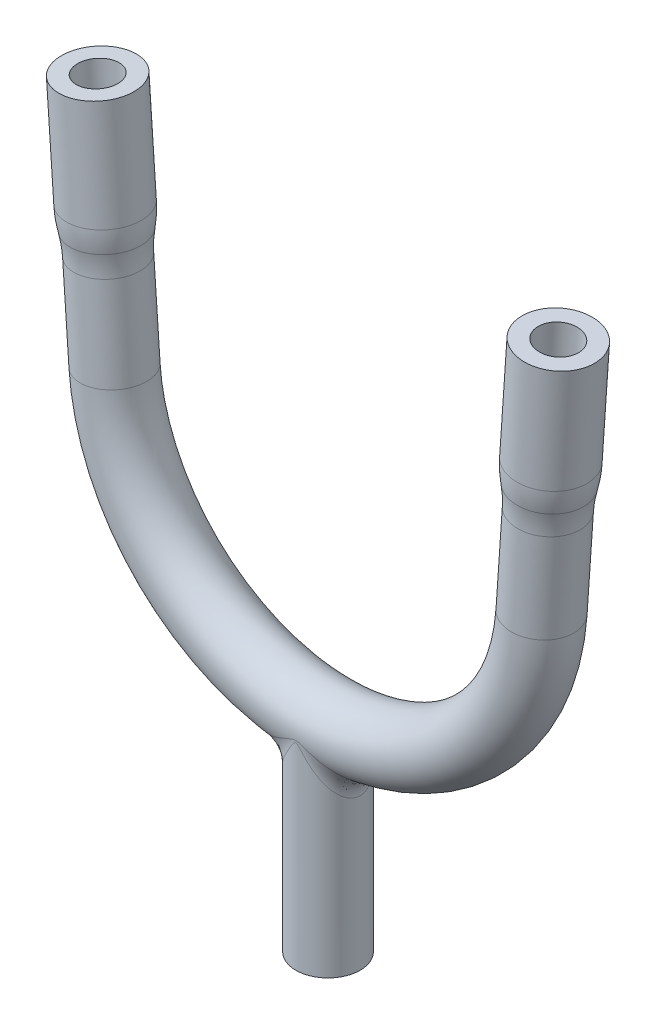
SolidWorks part; units mm, degrees
ref_plane "Alzado" through (0, 0, 0) normal (0, 0, 1) x (1, 0, 0)
ref_plane "Planta" through (0, 0, 0) normal (0, 1, 0) x (1, 0, 0)
ref_plane "Vista lateral" through (0, 0, 0) normal (1, 0, 0) x (0, 0, -1)
sketch "Croquis1" plane through (0, 0, 0) normal (0, 0, 1) x (1, 0, 0)
  line L0 (0, 0) -> (0, 191.7552) construction
  line L1 (5, 160.1093) -> (40.914, 157.6226) construction
  line L2 (40.914, 157.6226) -> (30, 0) construction
  line L3 (27.506, 0.1727) -> (38.5804, 160.1115) construction
  line L4 (27.506, 0.1727) -> (30, 0) construction
  line L5 (5, 160.1093) -> (4.8273, 157.6153) construction
  line L6 (4.8273, 157.6153) -> (-19.3231, 159.2875) construction
  line L7 (24.0182, -50.199) -> (31.2919, 54.8506) construction
  circle A0 centre (27.506, 0.1727) radius 2.5 construction
  spline S0 degree 3 poles (4.8273, 157.6153) (36.4183, 155.4279) (39.0186, 166.4413) (27.506, 0.1727) knots 0 0 0 0 1 1 1 1
  dimension "D5" = 5
  dimension "D6" = 95
  dimension "D7" = 500
  dimension "D1" = 30
  dimension "D2" = 10
  dimension "D3" = 36
  dimension "D4" = 158
ref_plane "Plano1" through (27.506, 0.1727, 0) normal (-0.0691, -0.9976, 0) x (-0.9976, 0.0691, 0)
sketch "Croquis6" plane through (0, 0, 0) normal (0, 1, 0) x (1, 0, 0)
  line L1 (-37.5, 2.5) -> (37.5, 2.5)
  line L2 (-37.5, 2.5) -> (-37.5, -2.5)
  line L3 (-37.5, -2.5) -> (37.5, -2.5)
  line L4 (37.5, 2.5) -> (37.5, -2.5)
  line L5 (-37.5, 2.5) -> (37.5, -2.5) construction
  line L6 (-37.5, -2.5) -> (37.5, 2.5) construction
  point P0 (0, 0)
  dimension "D1" = 5
  dimension "D2" = 75
sketch "Croquis11" plane through (0, 0, 0) normal (0, 0, 1) x (1, 0, 0)
  line L0 (27.506, 0.1727) -> (28.536, 15.1373)
  line L1 (0, 0) -> (0, -39.8273) construction
  line L2 (27.506, 0.1727) -> (26.4525, -15.133)
  arc A0 (0, -39.8273) -> (26.4525, -15.133) centre (0, -13.3123) ccw
  spline S0 degree 3 poles (4.8273, 157.6153) (36.4183, 155.4279) (39.0186, 166.4413) (27.506, 0.1727) knots 0 0 0 0 1 1 1 1 construction
  dimension "D1" = 15
  dimension "D2" = 40
ref_plane "Plano2" through (28.536, 15.1373, 0) normal (0.0687, 0.9976, 0) x (0.9976, -0.0687, 0)
sketch "Croquis12" plane through (28.536, 15.1373, 0) normal (0.0687, 0.9976, 0) x (0.9976, -0.0687, 0)
  circle A0 centre (0, 0) radius 4
  dimension "D1" = 8
sweep "Barrer1" add profiles "Croquis12" path "Croquis11"
sketch "Croquis13" plane through (1.1716, 17.0208, 0) normal (0.0687, 0.9976, 0) x (0.9976, -0.0687, 0)
  circle A2 centre (27.4292, 0) radius 4.5
  circle A3 centre (27.4292, 0) radius 4.5
  dimension "D1" = 0.5
extrude "Saliente-Extruir1" add sketch "Croquis13" against normal blind 15
fillet "Redondeo3" radius 15 1 edges at (23.5154, 0.4474, 0)
fillet "Redondeo4" radius 15 1 edges at (23.0166, 0.4817, 0)
mirror "Simetría7" about plane through (0, 0, 0) normal (1, 0, 0) of bodies 138
sketch "Croquis14" plane through (0, 0, 0) normal (0, 0, 1) x (1, 0, 0)
  line L0 (0, -39.8273) -> (0, -64.8273)
  line L1 (0, -35.8273) -> (0, -43.8273) construction
  dimension "D1" = 25
ref_plane "Plano3" through (0, -64.8273, 0) normal (0, -1, 0) x (-1, 0, 0)
sketch "Croquis15" plane through (0, -64.8273, 0) normal (0, -1, 0) x (-1, 0, 0)
  circle A0 centre (0, 0) radius 3.975
  dimension "D1" = 7.95
extrude "Saliente-Extruir2" add sketch "Croquis15" against normal up to vertex (25 mm away) up to point (0, -39.8273, 0)
fillet "Redondeo5" radius 3 1 edges at (-0.0002, -40.2738, -3.975)
sketch "Sketch1" plane through (1.1716, 17.0208, 0) normal (0.0687, 0.9976, 0) x (0.9976, -0.0687, 0)
  circle A0 centre (27.4292, 0) radius 2.5
  dimension "D1" = 5
sketch "Sketch2" plane through (0, 0, 0) normal (0, 0, 1) x (1, 0, 0)
  line L0 (28.536, 15.1373) -> (27.506, 0.1727)
  line L1 (27.506, 0.1727) -> (26.4525, -15.133)
  line L2 (0, 0) -> (0, -39.8273) construction
  line L3 (-27.506, 0.1727) -> (-26.4525, -15.133)
  line L4 (-28.536, 15.1373) -> (-27.506, 0.1727)
  arc A0 (26.4525, -15.133) -> (-26.4525, -15.133) centre (0, -13.3123) cw
sweep "Cut-Sweep2" cut profiles "Sketch1" path "Sketch2"
sketch "Sketch3" plane through (0, -64.8273, 0) normal (0, -1, 0) x (1, 0, 0)
  circle A0 centre (0, 0) radius 2.5
  dimension "D1" = 5
extrude "Cut-Extrude1" cut sketch "Sketch3" against normal blind 25 contours A0
